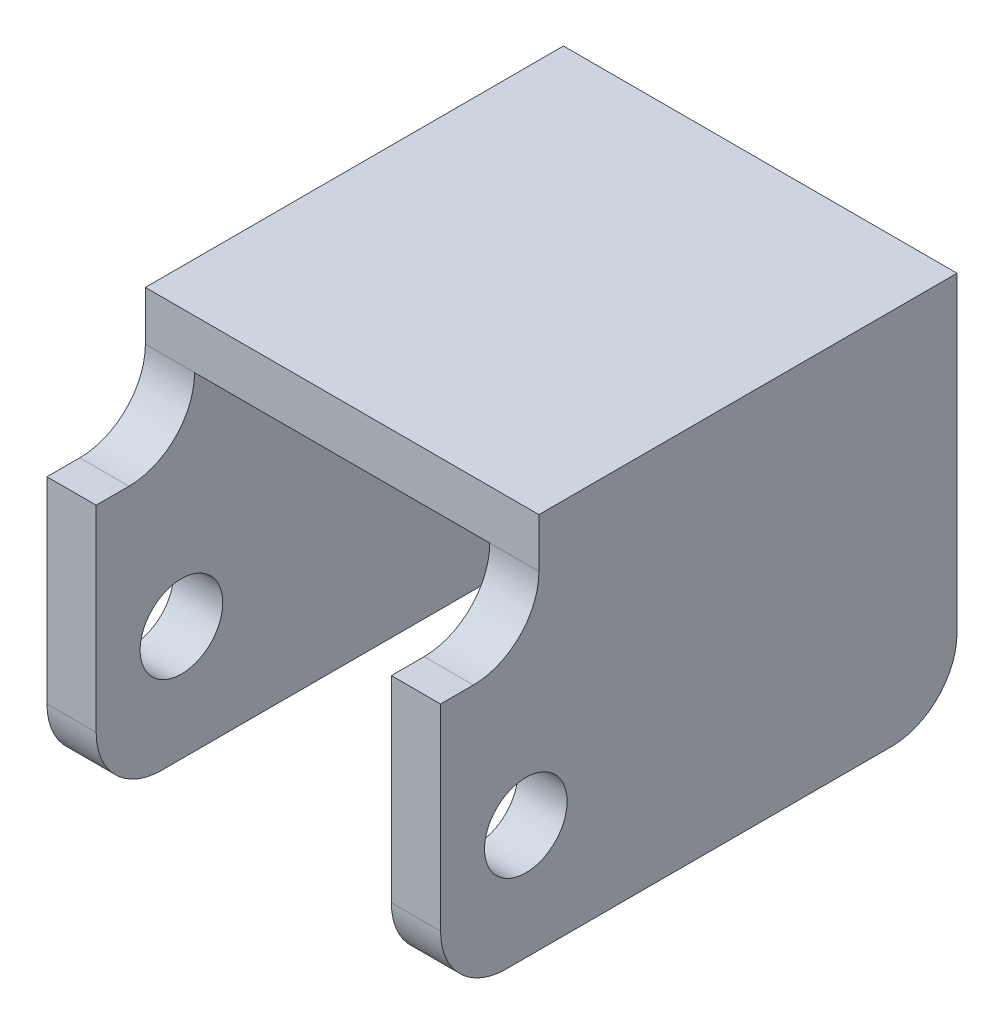
SolidWorks part; units mm, degrees
note: The reader was unsure of these and kept them because the rebuilt part matched: shared geometry of "Sketch1<3>".
material "6061-T6 (SS)"
ref_plane "Front Plane" through (0, 0, 0) normal (0, 0, 1) x (1, 0, 0)
ref_plane "Top Plane" through (0, 0, 0) normal (0, 1, 0) x (1, 0, 0)
ref_plane "Right Plane" through (0, 0, 0) normal (1, 0, 0) x (0, 0, -1)
sketch "Sketch1" plane through (0, 0, 0) normal (0, 1, 0) x (1, 0, 0)
  line L1 (-14.2875, -25) -> (14.2875, -25)
  line L2 (-14.2875, -25) -> (-14.2875, 25)
  line L3 (-14.2875, 25) -> (14.2875, 25)
  line L4 (14.2875, -25) -> (14.2875, 25)
  line L5 (-14.2875, -25) -> (14.2875, 25) construction
  line L6 (-14.2875, 25) -> (14.2875, -25) construction
  line L7 (14.2875, 25) -> (19.05, 25)
  line L8 (14.2875, 25) -> (14.2875, -25)
  line L9 (14.2875, -25) -> (19.05, -25)
  line L10 (19.05, 25) -> (19.05, -25)
  line L11 (-14.2875, 25) -> (-19.05, 25)
  line L12 (-14.2875, 25) -> (-14.2875, -25)
  line L13 (-14.2875, -25) -> (-19.05, -25)
  line L14 (-19.05, 25) -> (-19.05, -25)
  point P0 (0, 0)
  dimension "D1" = 38.1
  dimension "D2" = 50
  dimension "D3" = 4.7625
  dimension "D4" = 4.7625
extrude "Boss-Extrude1" add sketch "Sketch1" along normal blind 4.7625 contours L11 L14 L13 L2 | L1 L4 L3 L2 | L10 L7 L4 L9
extrude "Boss-Extrude2" add sketch "Sketch1<3>" against normal blind 31.75 contours L11 L14 L13 L2 | L10 L7 L4 L9
sketch "Sketch1<3>" plane through (0, 0, 0) normal (0, 1, 0) x (1, 0, 0) same geometry as "Sketch1"
sketch "Sketch3" plane through (19.05, 0, 0) normal (1, 0, 0) x (0, 0, -1)
  line L0 (25, 0) -> (-12.3, -31.75)
  line L1 (25, 0) -> (-25, 0) construction
  line L2 (-12.3, -31.75) -> (-25, -31.75)
  line L3 (-15.475, -6.35) -> (-25, -6.35)
  line L4 (-25, 4.7625) -> (-25, -31.75)
  line L5 (-25, -31.75) -> (25, -31.75)
  line L6 (25, -31.75) -> (25, 4.7625)
  line L7 (25, 4.7625) -> (-25, 4.7625)
  line L8 (-25, 4.7625) -> (-25, -31.75)
  line L9 (-25, -31.75) -> (25, -31.75)
  line L10 (25, -31.75) -> (25, 4.7625)
  line L11 (25, 4.7625) -> (-25, 4.7625)
  line L12 (-25, 0) -> (-25, -31.75)
  line L13 (-15.475, -6.35) -> (-15.475, 4.7625)
  line L14 (-25, 4.7625) -> (-25, -31.75) construction
  line L18 (-25, 0) -> (25, 0) construction
  circle A0 centre (-16.745, -20.6375) radius 4
  dimension "D4" = 8
  dimension "D2" = 6.35
  dimension "D3" = 12.7
  dimension "D5" = 25.4
  dimension "D6" = 9.525
  dimension "D7" = 1.27
  dimension "D1" = 0
extrude "Cut-Extrude1" cut sketch "Sketch3" against normal through all
fillet "Fillet1" radius 6.35 6 edges at (-16.6688, -31.75, 25) (16.6688, -31.75, 25) (-16.6688, -31.75, -25) (16.6687, -31.75, -25) (-16.6688, -6.35, 15.475) (16.6688, -6.35, 15.475)
